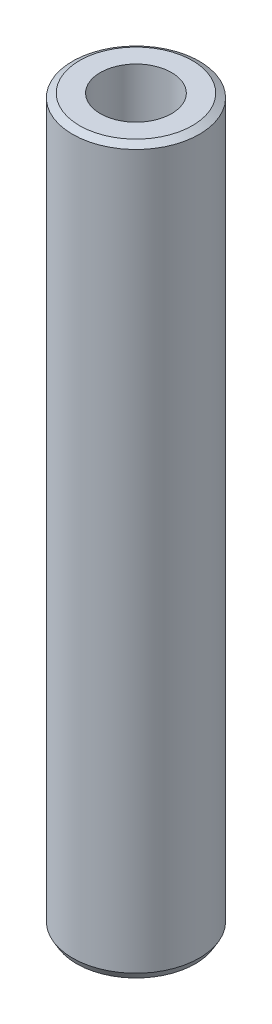
SolidWorks part; units mm, degrees
ref_plane "Front Plane" through (0, 0, 0) normal (0, 0, 1) x (1, 0, 0)
ref_plane "Top Plane" through (0, 0, 0) normal (0, 1, 0) x (1, 0, 0)
ref_plane "Right Plane" through (0, 0, 0) normal (1, 0, 0) x (0, 0, -1)
sketch "Sketch1" plane through (0, 0, 0) normal (0, 1, 0) x (1, 0, 0)
  circle A0 centre (0, 0) radius 32.5
  dimension "SHAFT_OD" = 65
extrude "Boss-Extrude1" add sketch "Sketch1" along normal blind 371.419
sketch "Sketch2" plane through (0, 0, 0) normal (0, 1, 0) x (1, 0, 0)
  circle A0 centre (0, 0) radius 18.2742
  dimension "BORE_D" = 36.5483
extrude "Cut-Extrude1" cut sketch "Sketch2" along normal through all
chamfer "Chamfer1" distance 2.0666 angle 60 2 edges at (0, 371.419, 32.5) (0, 0, 32.5) first distance on face at (0, 371.419, 32.5) first distance on face at (0, 0, 18.2742)
